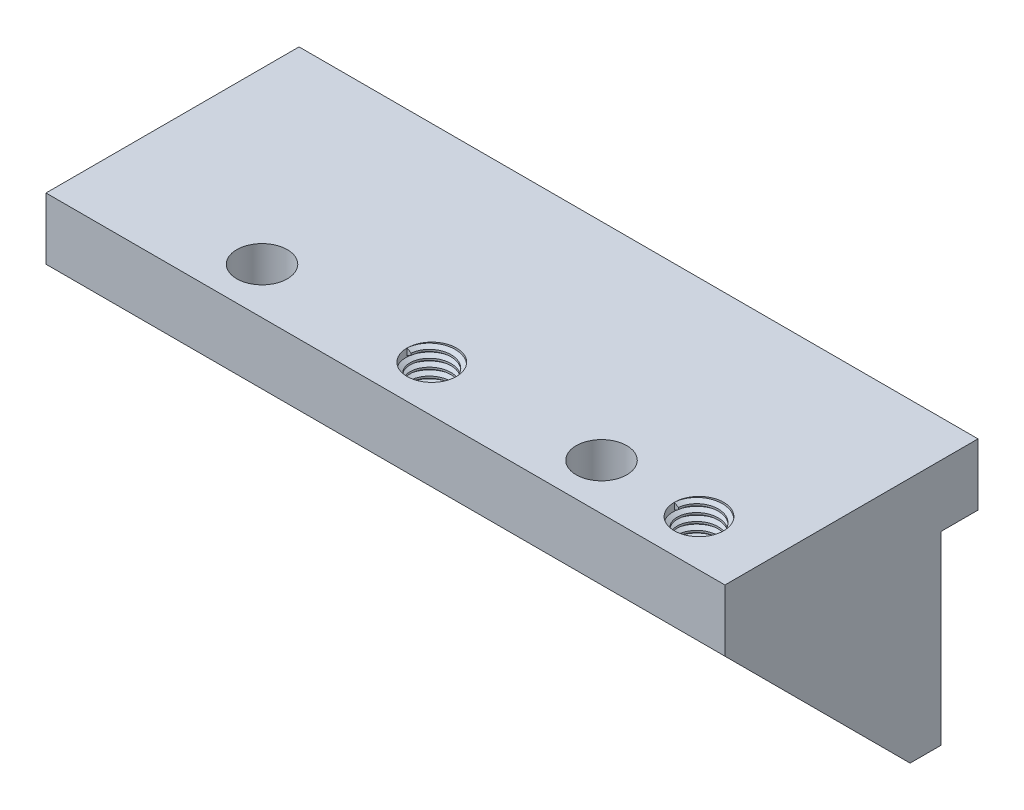
SolidWorks part; units mm, degrees
ref_plane "Front Plane" through (0, 0, 0) normal (0, 0, 1) x (1, 0, 0)
ref_plane "Top Plane" through (0, 0, 0) normal (0, 1, 0) x (1, 0, 0)
ref_plane "Right Plane" through (0, 0, 0) normal (1, 0, 0) x (0, 0, -1)
sketch "Sketch1" plane through (0, 0, 0) normal (0, 0, 1) x (1, 0, 0)
  line L0 (-55, 0) -> (0, 0) construction
  line L1 (-55, 15) -> (55, 15)
  line L2 (-55, 15) -> (-55, -15)
  line L3 (-55, -15) -> (55, -15)
  line L4 (55, 15) -> (55, -15)
  line L5 (-55, 15) -> (55, -15) construction
  line L6 (-55, -15) -> (55, 15) construction
  line L7 (0, 0) -> (55, 0) construction
  circle A0 centre (27.5, 0) radius 3.1
  circle A1 centre (-27.5, 0) radius 3.1
  point P0 (0, 0)
extrude "Boss-Extrude1" add sketch "Sketch1" along normal blind 5
sketch "Sketch2" plane through (0, 15, 0) normal (0, 1, 0) x (1, 0, 0)
  line L0 (49.4745, -35) -> (49.4745, -20) construction
  line L2 (-55, -5) -> (-55, 6)
  line L3 (-55, 6) -> (55, 6)
  line L4 (55, -5) -> (55, 6)
  line L5 (-55, -5) -> (55, -5)
  line L6 (-55, -5) -> (-55, -35)
  line L7 (-55, -35) -> (55, -35)
  line L8 (55, -5) -> (55, -35)
  line L9 (55, -27.5) -> (0, -27.5) construction
  line L10 (0, -35) -> (0, -27.5) construction
  line L11 (0, -27.5) -> (-55, -27.5) construction
  line L12 (31.6, -27.5) -> (31.6, -32.1487) construction
  line L13 (31.6, -32.1487) -> (55, -32.1487) construction
  line L14 (43.3, -32.1487) -> (43.3, -27.5) construction
  circle A0 centre (-27.5, -27.5) radius 4.1
  circle A1 centre (27.5, -27.5) radius 4.1
  circle A2 centre (43.3, -27.5) radius 4
  circle A3 centre (0, -27.5) radius 4
  line M9 (55, 0) -> (-55, 0)
  line M10 (-55, 0) -> (-55, -5)
  line M11 (-55, -5) -> (55, -5)
  line M12 (55, -5) -> (55, 0)
extrude "Boss-Extrude2" add sketch "Sketch2" along normal blind 10 contours L8 L6 L7 M11 | L4 L3 L2 M9 | M12 M9 M10 M11 region at (0, 15, 2.5) region at (-0.7035, 15, 19.5003) region at (0, 15, -3)
sketch "Sketch3" plane through (55, 0, 0) normal (1, 0, 0) x (0, 0, -1)
  line L0 (-35, 15) -> (-5, -15)
  line L1 (-5, -15) -> (-5, 15)
  line L2 (-5, 15) -> (-35, 15)
extrude "Boss-Extrude3" add sketch "Sketch3" against normal through all
ref_plane "Plane1" through (0, 0, 5) normal (0, 0, 1) x (1, 0, 0)
sketch "Sketch4" plane through (0, 0, 5) normal (0, 0, 1) x (1, 0, 0)
  line L0 (-55, -15) -> (55, -15) construction
  line L1 (-51, 15) -> (51, 15)
  line L2 (-51, 15) -> (-51, -15)
  line L3 (-51, -15) -> (51, -15)
  line L4 (51, 15) -> (51, -15)
  line L5 (-51, 15) -> (51, -15) construction
  line L6 (-51, -15) -> (51, 15) construction
  point P0 (0, 0)
extrude "Cut-Extrude1" cut sketch "Sketch4" along normal through all
thread "Thread1" pitch 1.25 method extrude profile "Thread Profile1" start angle 0, offset 0, length 8.9, pitch 1.25, diameter 8
ref_plane "Plane2" through (39.3, 25, 27.5) normal (0, 0, 1) x (-1, 0, 0)
sketch "Thread Profile1" plane through (39.3, 25, 27.5) normal (0, 0, 1) x (-1, 0, 0)
  line L0 (0, 0) -> (0, 1.25) construction
  line L11 (0, 0) -> (0, 1.0937)
  line L12 (0, 1.0937) -> (-0.6766, 0.7031)
  line L13 (-0.6766, 0.7031) -> (-0.6766, 0.3906)
  line L15 (-0.6766, 0.3906) -> (0, 0)
  line L17 (-0.6766, 0.5469) -> (0, 0.5469) construction
  point P2 (0, 0)
  dimension "Pitch" = 1.25
  dimension "Profile_Angle" = 60
  dimension "Profile_Land" = 0.3125
  dimension "Profile_Height" = 0.6766
thread "Thread2" pitch 1.25 method extrude profile "Thread Profile2" start angle 0, offset 0, length 8.9, pitch 1.25, diameter 8
ref_plane "Plane3" through (-4, 25, 27.5) normal (0, 0, 1) x (-1, 0, 0)
sketch "Thread Profile2" plane through (-4, 25, 27.5) normal (0, 0, 1) x (-1, 0, 0)
  line L0 (0, 0) -> (0, 1.25) construction
  line L11 (0, 0) -> (0, 1.0937)
  line L12 (0, 1.0937) -> (-0.6766, 0.7031)
  line L13 (-0.6766, 0.7031) -> (-0.6766, 0.3906)
  line L15 (-0.6766, 0.3906) -> (0, 0)
  line L17 (-0.6766, 0.5469) -> (0, 0.5469) construction
  point P2 (0, 0)
  dimension "Pitch" = 1.25
  dimension "Profile_Angle" = 60
  dimension "Profile_Land" = 0.3125
  dimension "Profile_Height" = 0.6766
